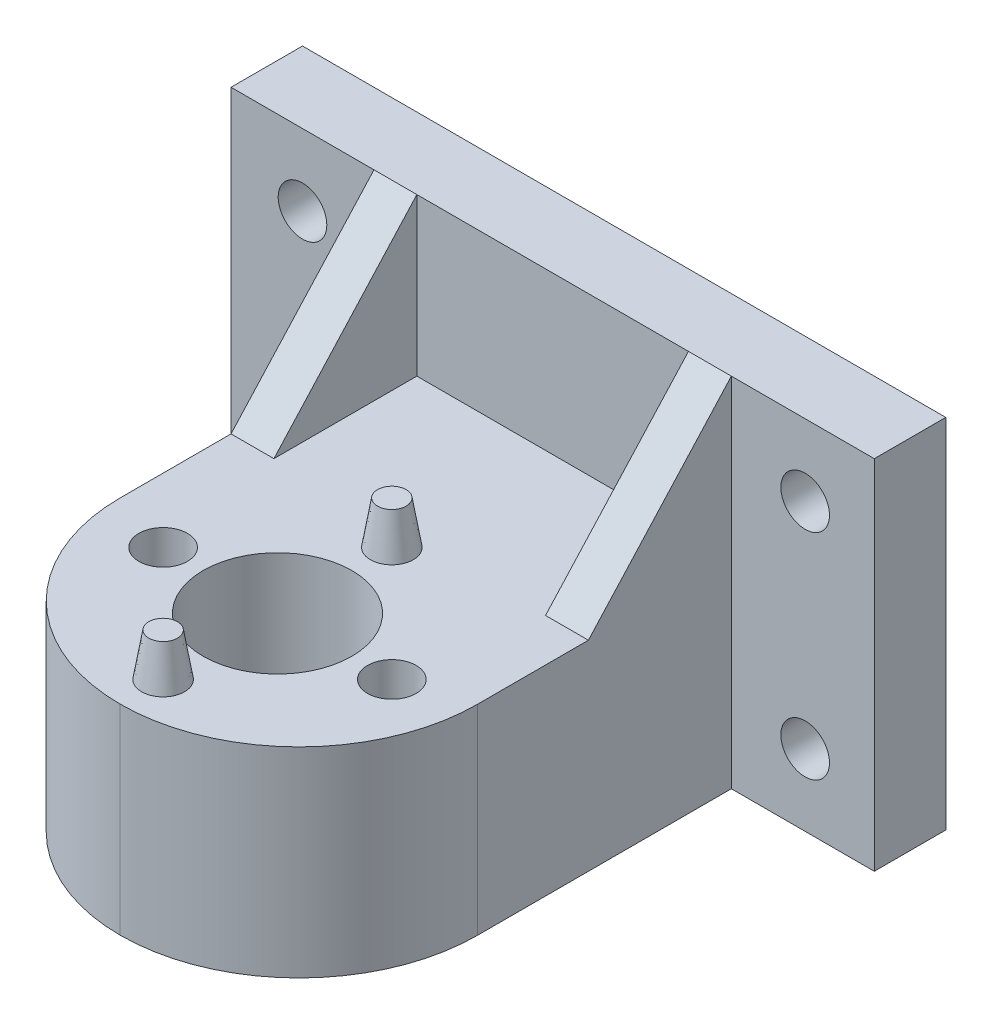
SolidWorks part; units mm, degrees
material "Custom Plastic"
ref_plane "Front Plane" through (0, 0, 0) normal (0, 0, 1) x (1, 0, 0)
ref_plane "Top Plane" through (0, 0, 0) normal (0, 1, 0) x (1, 0, 0)
ref_plane "Right Plane" through (0, 0, 0) normal (1, 0, 0) x (0, 0, -1)
sketch "Sketch1" plane through (0, 0, 0) normal (0, 0, 1) x (1, 0, 0)
  line L0 (-111.6238, 235.9236) -> (-111.6238, 210.9236) construction
  line L1 (-111.6238, 235.9236) -> (-99.1238, 235.9236)
  line L2 (-129.1238, 235.9236) -> (-129.1238, 230.9236)
  line L3 (-124.1238, 235.9236) -> (-134.1238, 235.9236)
  line L4 (-264.0238, 235.9236) -> (-264.0238, 210.9236)
  line L5 (-264.0238, 210.9236) -> (40.7762, 210.9236)
  line L6 (40.7762, 210.9236) -> (40.7762, 235.9236)
  line L7 (40.7762, 235.9236) -> (-264.0238, 235.9236)
  line L8 (-264.0238, 235.9236) -> (-264.0238, 210.9236)
  line L9 (-264.0238, 210.9236) -> (40.7762, 210.9236)
  line L10 (40.7762, 210.9236) -> (40.7762, 235.9236)
  line L14 (-98.9021, 210.9236) -> (-123.9021, 210.9236)
  line L18 (-123.9021, 210.9236) -> (-133.9021, 210.9236)
  line L20 (-99.1238, 235.9236) -> (-124.1238, 235.9236)
  line L21 (-99.1238, 235.9236) -> (-99.1238, 210.9236)
  line L22 (-124.1238, 235.9236) -> (-124.1238, 210.9236)
  line L23 (-99.1238, 210.9236) -> (-124.1238, 210.9236)
  line L24 (-124.1238, 235.9236) -> (-124.1238, 210.9236)
  line L25 (-124.1238, 210.9236) -> (-134.1238, 210.9236)
  line L26 (-134.1238, 235.9236) -> (-134.1238, 210.9236)
  line L27 (-99.1238, 235.9236) -> (-89.1238, 235.9236)
  line L28 (-99.1238, 235.9236) -> (-99.1238, 210.9236)
  line L29 (-99.1238, 210.9236) -> (-89.1238, 210.9236)
  line L30 (-89.1238, 235.9236) -> (-89.1238, 210.9236)
  line L31 (-129.1238, 210.9236) -> (-129.1238, 215.9236)
  line L32 (-93.9602, 235.9236) -> (-93.9602, 230.9236)
  line L33 (-93.9602, 210.9236) -> (-93.9602, 215.9236)
  circle A0 centre (-129.1238, 230.9236) radius 1.7
  circle A1 centre (-129.1238, 215.9236) radius 1.7
  circle A2 centre (-93.9602, 230.9236) radius 1.7
  circle A3 centre (-93.9602, 215.9236) radius 1.7
  dimension "D1" = 0
extrude "Boss-Extrude1" add sketch "Sketch1" along normal blind 5 contours L1 L0 L23 L21 | L0 L20 L22 L18 L9 | A1 L25 L22 L3 A0 L26 L9 | A3 L29 L30 L27 A2 L21 L14 L9 region at (-105.3738, 223.4236, 0) region at (-117.8738, 223.4236, 0) region at (-94.1366, 223.4236, 0) region at (-129.1238, 223.4236, 0)
sketch "Sketch2" plane through (0, 210.9236, 0) normal (0, -1, 0) x (1, 0, 0)
  line L1 (-89.1238, 0) -> (-134.1238, 0)
  line L4 (-134.1238, 0) -> (-89.1238, 0)
  line L5 (-89.1238, 0) -> (-89.1238, 5)
  line L6 (-89.1238, 5) -> (-134.1238, 5)
  line L7 (-134.1238, 5) -> (-134.1238, 0)
  line L8 (-134.1238, 0) -> (-89.1238, 0)
  line L9 (-89.1238, 0) -> (-89.1238, 5)
  line L10 (-89.1238, 5) -> (-134.1238, 5)
  line L11 (-134.1238, 5) -> (-134.1238, 0)
  line L14 (-111.6238, 0) -> (-111.6238, 35.25)
  line L15 (-111.6238, 35.25) -> (-124.1238, 35.25)
  line L16 (-124.1238, 35.25) -> (-99.1238, 35.25)
  line L18 (-99.1238, 35.25) -> (-124.1238, 35.25)
  line L19 (-99.1238, 35.25) -> (-99.1238, 5)
  line L20 (-99.1238, 5) -> (-124.1238, 5)
  line L21 (-124.1238, 35.25) -> (-124.1238, 5)
  circle A0 centre (-111.6238, 24.25) radius 11 construction
  circle A1 centre (-111.6238, 24.25) radius 11 construction
  circle A4 centre (-111.6238, 24.25) radius 5.2
  circle A5 centre (-105.3606, 19.2728) radius 1.95 construction
  circle A6 centre (-105.3606, 19.2728) radius 1.95 construction
  circle A7 centre (-111.6238, 24.25) radius 8 construction
  circle A8 centre (-103.6238, 24.25) radius 1.7
  circle A9 centre (-119.6238, 24.25) radius 1.7
  dimension "D1" = 0
extrude "Boss-Extrude2" add sketch "Sketch2" against normal up to surface (14 mm away) contours A4 L14 L10 L19 L16 A8 | A4 L14 L15 L21 L10 A9 region at (-104.8966, 210.9236, 19.4738) region at (-118.351, 210.9236, 19.4738)
sketch "Sketch3" plane through (0, 224.9236, 0) normal (0, 1, 0) x (1, 0, 0)
  circle A0 centre (-111.6238, -24.25) radius 11 construction
  circle A1 centre (-111.6238, -24.25) radius 11 construction
  circle A2 centre (-111.6238, -24.25) radius 8
  circle A3 centre (-111.6238, -16.25) radius 1.5
  circle A4 centre (-111.6238, -32.25) radius 1.5
extrude "Boss-Extrude3" add sketch "Sketch3" along normal blind 3 contours A2 A3 | A2 A3 | A2 A4 | A2 A4 region at (-111.6238, 224.9236, 16.9113) region at (-111.6238, 224.9236, 15.6394) region at (-111.6238, 224.9236, 32.8606) region at (-111.6238, 224.9236, 31.5887)
chamfer "Chamfer1" distance 3 distance2 0.5 2 edges at (-111.6238, 227.9236, 33.75) (-111.6238, 227.9236, 17.75) first distance on face at (-111.6238, 227.9236, 33.75) first distance on face at (-111.6238, 227.9236, 17.75)
fillet "Fillet1" radius 12.5 2 edges at (-99.1238, 217.9236, 35.25) (-124.1238, 217.9236, 35.25)
sketch "Sketch4" plane through (0, 224.9236, 0) normal (0, 1, 0) x (1, 0, 0)
  line L1 (-124.1238, -5) -> (-121.1238, -5)
  line L2 (-124.1238, -5) -> (-124.1238, -15)
  line L9 (-124.1238, -15) -> (-121.1238, -15)
  line L10 (-121.1238, -5) -> (-121.1238, -15)
  line L11 (-99.1238, -5) -> (-102.1238, -5)
  line L12 (-99.1238, -5) -> (-99.1238, -15)
  line L13 (-99.1238, -15) -> (-102.1238, -15)
  line L14 (-102.1238, -5) -> (-102.1238, -15)
extrude "Boss-Extrude4" add sketch "Sketch4" along normal up to surface (11 mm away) up to face at (-111.6238, 235.9236, 2.5)
chamfer "Chamfer2" distance 11 distance2 10 2 edges at (-100.6238, 235.9236, 15) (-122.6238, 235.9236, 15) first distance on face at (-100.6238, 230.4236, 15) first distance on face at (-122.6238, 230.4236, 15)
